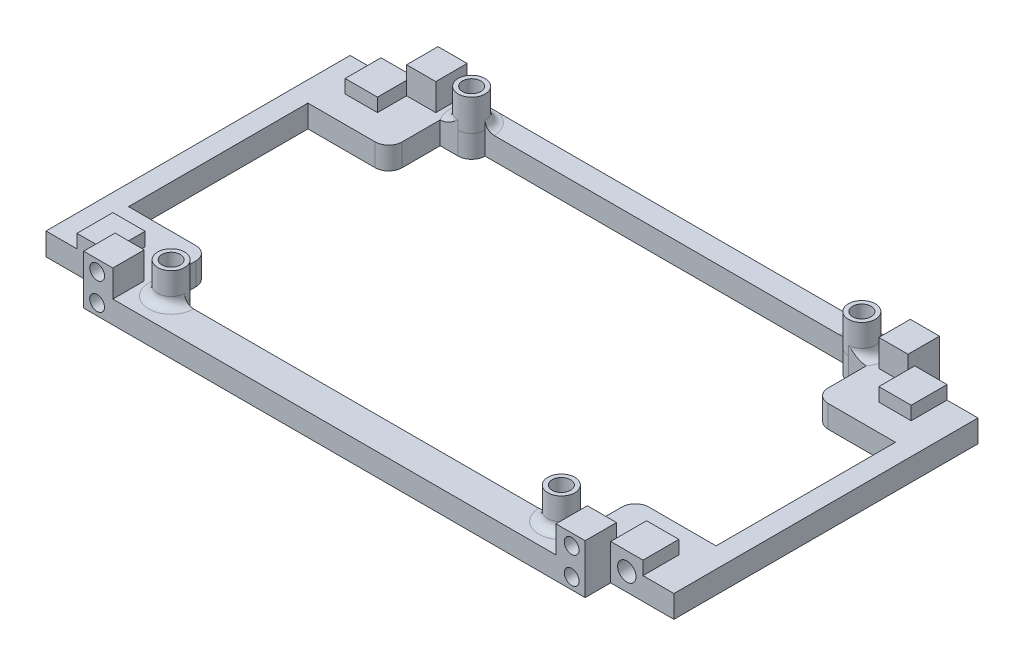
SolidWorks part; units mm, degrees
ref_plane "Front Plane" through (0, 0, 0) normal (0, 0, 1) x (1, 0, 0)
ref_plane "Top Plane" through (0, 0, 0) normal (0, 1, 0) x (1, 0, 0)
ref_plane "Right Plane" through (0, 0, 0) normal (1, 0, 0) x (0, 0, -1)
sketch "Sketch1" plane through (0, 0, 0) normal (0, 1, 0) x (1, 0, 0)
  line L0 (-70, -33.9) -> (-70, 33.9)
  line L1 (-70, -41) -> (70, -41) construction
  line L2 (-70, -41) -> (-70, 41) construction
  line L3 (-70, 41) -> (70, 41) construction
  line L4 (70, -41) -> (70, 41) construction
  line L5 (-70, -41) -> (70, 41) construction
  line L6 (-70, 41) -> (70, -41) construction
  line L7 (-70, 33.9) -> (-55.9, 33.9)
  line L8 (-55.9, 33.9) -> (-55.9, 41)
  line L9 (-55.9, 41) -> (55.9, 41)
  line L10 (55.9, 41) -> (55.9, 33.9)
  line L11 (55.9, 33.9) -> (70, 33.9)
  line L12 (70, 33.9) -> (70, -33.9)
  line L13 (70, -33.9) -> (55.9, -33.9)
  line L14 (55.9, -33.9) -> (55.9, -41)
  line L15 (55.9, -41) -> (-55.9, -41)
  line L16 (-55.9, -41) -> (-55.9, -33.9)
  line L17 (-55.9, -33.9) -> (-70, -33.9)
  point P0 (0, 0)
  dimension "D1" = 140
  dimension "D2" = 82
  dimension "D3" = 7.1
  dimension "D4" = 14.1
extrude "Boss-Extrude1" add sketch "Sketch1" along normal blind 5
sketch "Sketch3" plane through (0, 5, 0) normal (0, 1, 0) x (1, 0, 0)
  line L1 (-43.5, 34.5) -> (43.5, 34.5) construction
  line L2 (-43.5, 34.5) -> (-43.5, -32.5) construction
  line L3 (-43.5, -32.5) -> (43.5, -32.5) construction
  line L4 (43.5, 34.5) -> (43.5, -32.5) construction
  line L5 (-43.5, 34.5) -> (43.5, -32.5) construction
  line L6 (-43.5, -32.5) -> (43.5, 34.5) construction
  circle A0 centre (-43.5, -32.5) radius 3
  circle A1 centre (43.5, -32.5) radius 3
  circle A2 centre (43.5, 34.5) radius 3
  circle A3 centre (-43.5, 34.5) radius 3
  point P0 (0, 1)
  dimension "D4" = 6
  dimension "D1" = 87
  dimension "D2" = 67
  dimension "D3" = 1
sketch "Sketch2" plane through (0, 5, 0) normal (0, 1, 0) x (1, 0, 0)
  line L0 (-43.5, 31.5) -> (-40.5, 31.5)
  line L5 (-40.5, -32.5) -> (40.5, -32.5)
  line L6 (-43.5, -29.5) -> (-43.5, 31.5)
  line L7 (-40.5, 34.5) -> (40.5, 34.5)
  line L8 (43.5, -29.5) -> (43.5, 31.5)
  line L9 (-43.5, -32.5) -> (43.5, 34.5) construction
  line L10 (-43.5, 34.5) -> (43.5, -32.5) construction
  line L11 (-40.5, 31.5) -> (-40.5, 34.5)
  line L12 (40.5, 34.5) -> (40.5, 31.5)
  line L13 (40.5, 31.5) -> (43.5, 31.5)
  line L14 (43.5, -29.5) -> (40.5, -29.5)
  line L15 (40.5, -29.5) -> (40.5, -32.5)
  line L16 (-40.5, -32.5) -> (-40.5, -29.5)
  line L17 (-40.5, -29.5) -> (-43.5, -29.5)
  line L18 (43.5, -32.5) -> (-43.5, -32.5) construction
  line L19 (-43.5, -32.5) -> (-43.5, 34.5) construction
  line L20 (-43.5, 34.5) -> (43.5, 34.5) construction
  line L21 (43.5, 34.5) -> (43.5, -32.5) construction
  point P0 (0, 0)
  point P1 (0, 1)
  dimension "D1" = 3
extrude "Cut-Extrude1" cut sketch "Sketch2" against normal through all
extrude "Boss-Extrude2" add sketch "Sketch3" along normal blind 7
sketch "Sketch4" plane through (0, 12, 0) normal (0, 1, 0) x (1, 0, 0)
  circle A0 centre (-43.5, 34.5) radius 2.05
  circle A1 centre (43.5, 34.5) radius 2.05
  circle A2 centre (43.5, -32.5) radius 2.05
  circle A3 centre (-43.5, -32.5) radius 2.05
  dimension "D1" = 4.1
extrude "Cut-Extrude2" cut sketch "Sketch4" against normal through all and the other way through all
sketch "Sketch5" plane through (0, 5, 0) normal (0, 1, 0) x (1, 0, 0)
  line L0 (-43.5, -29.5) -> (-40.5, -29.5) construction
  line L1 (-43.5, 31.5) -> (-55.5, 31.5)
  line L2 (-43.5, 31.5) -> (-43.5, -29.5)
  line L3 (-43.5, -29.5) -> (-55.5, -29.5)
  line L4 (-55.5, 31.5) -> (-55.5, -29.5)
  line L5 (0, 34.5) -> (0, -32.5) construction
  line L6 (40.5, 34.5) -> (-40.5, 34.5) construction
  line L7 (-40.5, -32.5) -> (40.5, -32.5) construction
  line L8 (55.5, 31.5) -> (55.5, -29.5)
  line L9 (43.5, -29.5) -> (55.5, -29.5)
  line L10 (43.5, 31.5) -> (43.5, -29.5)
  line L11 (43.5, 31.5) -> (55.5, 31.5)
  dimension "D1" = 12
extrude "Cut-Extrude3" cut sketch "Sketch5" against normal through all
fillet "Fillet1" radius 3 4 edges at (40.5, 2.5, 29.5) (-40.5, 2.5, 29.5) (40.5, 2.5, -31.5) (-40.5, 2.5, -31.5)
sketch "Sketch6" plane through (0, 5, 0) normal (0, 1, 0) x (1, 0, 0)
  line L0 (40.5, 34.5) -> (-40.5, 34.5) construction
  line L1 (-25, 34.5) -> (25, 34.5)
  line L2 (-25, 34.5) -> (-25, 32.5)
  line L3 (-25, 32.5) -> (25, 32.5)
  line L4 (25, 34.5) -> (25, 32.5)
  line L5 (0, -32.5) -> (0, -41) construction
  line L6 (-40.5, -32.5) -> (40.5, -32.5) construction
  line L7 (-55.9, -41) -> (55.9, -41) construction
  line L8 (0, 32.5) -> (0, 41) construction
  line L9 (55.9, 41) -> (-55.9, 41) construction
  point P6 (0, 32.5)
  dimension "D1" = 50
sketch "Sketch7" plane through (0, 5, 0) normal (0, 1, 0) x (1, 0, 0)
  line L0 (0, 41) -> (0, -41) construction
  line L1 (55.9, 33.9) -> (63.1, 33.9)
  line L2 (55.9, 33.9) -> (55.9, 25.9)
  line L3 (55.9, 25.9) -> (63.1, 25.9)
  line L4 (63.1, 33.9) -> (63.1, 25.9)
  line L5 (55.9, 41) -> (-55.9, 41) construction
  line L6 (-55.9, -41) -> (55.9, -41) construction
  line L7 (-70, 0) -> (70, 0) construction
  line L8 (-70, 33.9) -> (-70, -33.9) construction
  line L9 (70, -33.9) -> (70, 33.9) construction
  dimension "D1" = 7.2
  dimension "D2" = 8
extrude "Boss-Extrude3" add sketch "Sketch7" along normal blind 3
sketch "Sketch8" plane through (0, 0, -33.9) normal (0, 0, -1) x (-1, 0, 0)
  line L0 (-63.1, 8) -> (-55.9, 0) construction
  circle A0 centre (-59.5, 4) radius 2.05
  dimension "D1" = 4.1
extrude "Cut-Extrude5" cut sketch "Sketch8" against normal blind 6
mirror "Mirror3" about plane through (0, 0, 0) normal (1, 0, 0) of "Cut-Extrude5", "Boss-Extrude3"
mirror "Mirror4" about plane through (0, 0, 0) normal (0, 0, 1) of "Mirror3"
sketch "Sketch10" plane through (0, 5, 0) normal (0, 1, 0) x (1, 0, 0)
  line L0 (55.9, 33.9) -> (55.9, 41) construction
  line L1 (-55.9, 41) -> (55.9, 41)
  line L2 (-55.9, 41) -> (-55.9, 40)
  line L3 (-55.9, 40) -> (55.9, 40)
  line L4 (55.9, 41) -> (55.9, 40)
  line L5 (-55.9, -33.9) -> (-55.9, -41) construction
  line L6 (55.9, -41) -> (-55.9, -41)
  line L7 (55.9, -41) -> (55.9, -40)
  line L8 (55.9, -40) -> (-55.9, -40)
  line L9 (-55.9, -41) -> (-55.9, -40)
  dimension "D1" = 1
  dimension "D2" = 1
extrude "Cut-Extrude7" cut sketch "Sketch10" against normal through all
fillet "Fillet5" radius 2 4 edges at (45.6213, 5, -36.6213) (45.6213, 5, 34.6213) (-45.6213, 5, 34.6213) (-45.6213, 5, -36.6213)
sketch "Sketch11" plane through (0, 5, 0) normal (0, 1, 0) x (1, 0, 0)
  line L1 (55.5, -29.5) -> (47.5, -29.5)
  line L2 (55.5, -29.5) -> (55.5, 31.5)
  line L3 (55.5, 31.5) -> (47.5, 31.5)
  line L4 (47.5, -29.5) -> (47.5, 31.5)
  line L5 (-47.5, -29.5) -> (-55.5, -29.5)
  line L6 (-47.5, -29.5) -> (-47.5, 31.5)
  line L7 (-47.5, 31.5) -> (-55.5, 31.5)
  line L8 (-55.5, -29.5) -> (-55.5, 31.5)
extrude "Boss-Extrude4" add sketch "Sketch11" against normal up to surface (5 mm away) up to face at (0, 0, 0)
sketch "Sketch12" plane through (0, 5, 0) normal (0, 1, 0) x (1, 0, 0)
  line L0 (47.5, 31.5) -> (47.5, -29.5) construction
  line L1 (47.5, 20) -> (65.5, 20)
  line L2 (47.5, 20) -> (47.5, -20)
  line L3 (47.5, -20) -> (65.5, -20)
  line L4 (65.5, 20) -> (65.5, -20)
  line L5 (70, -33.9) -> (70, 33.9) construction
  point P6 (65.5, 0)
  point P9 (70, 0)
  dimension "D1" = 18
  dimension "D2" = 40
extrude "Cut-Extrude8" cut sketch "Sketch12" against normal through all and the other way through all
mirror "Mirror7" about plane through (0, 0, 0) normal (1, 0, 0) of "Cut-Extrude8"
fillet "Fillet6" radius 3 4 edges at (47.5, 2.5, -20) (47.5, 2.5, 20) (-47.5, 2.5, -20) (-47.5, 2.5, 20)
sketch "Sketch13" plane through (0, 5, 0) normal (0, 1, 0) x (1, 0, 0)
  line L0 (55.9, 33.9) -> (55.9, 40) construction
  line L1 (-55.9, 40) -> (55.9, 40)
  line L2 (-55.9, 40) -> (-55.9, 39.4)
  line L3 (-55.9, 39.4) -> (55.9, 39.4)
  line L4 (55.9, 40) -> (55.9, 39.4)
  line L5 (-55.9, -33.9) -> (-55.9, -40) construction
  line L6 (55.9, -40) -> (-55.9, -40)
  line L7 (55.9, -40) -> (55.9, -39.6)
  line L8 (55.9, -39.6) -> (-55.9, -39.6)
  line L9 (-55.9, -40) -> (-55.9, -39.6)
  dimension "D1" = 0.6
  dimension "D2" = 0.4
extrude "Cut-Extrude9" cut sketch "Sketch13" against normal through all both and the other way through all
sketch "Sketch14" plane through (0, 5, 0) normal (0, 1, 0) x (1, 0, 0)
  line L1 (-55.9, -39.6) -> (-49.4, -39.6)
  line L2 (-55.9, -39.6) -> (-55.9, -32.6)
  line L3 (-55.9, -32.6) -> (-49.4, -32.6)
  line L4 (-49.4, -39.6) -> (-49.4, -32.6)
  line L5 (-55.9, 39.4) -> (-49.4, 39.4)
  line L6 (-55.9, 39.4) -> (-55.9, 32.4)
  line L7 (-55.9, 32.4) -> (-49.4, 32.4)
  line L8 (-49.4, 39.4) -> (-49.4, 32.4)
  dimension "D1" = 6.5
  dimension "D2" = 7
extrude "Boss-Extrude5" add sketch "Sketch14" along normal blind 6
sketch "Sketch15" plane through (0, 0, 39.6) normal (0, 0, 1) x (1, 0, 0)
  line L0 (-49.4, 5) -> (-49.4, 0) construction
  line L1 (55.9, 0) -> (-55.9, 0) construction
  line L3 (-55.9, 0) -> (-55.9, 11) construction
  circle A0 centre (-52.9, 2.5) radius 1.65
  circle A1 centre (-52.9, 8.5) radius 1.65
  point P4 (-49.4, 2.5)
  dimension "D1" = 3.3
  dimension "D2" = 3
  dimension "D3" = 6
extrude "Cut-Extrude10" cut sketch "Sketch15" against normal blind 6
sketch "Sketch16" plane through (0, 0, -39.4) normal (0, 0, -1) x (-1, 0, 0)
  circle A0 centre (52.9, 8.5) radius 1.65 construction
  circle A1 centre (52.9, 2.5) radius 1.65 construction
  circle A2 centre (52.9, 8.5) radius 1.65
  circle A3 centre (52.9, 2.5) radius 1.65
extrude "Cut-Extrude11" cut sketch "Sketch16" against normal blind 6
mirror "Mirror8" about plane through (0, 0, 0) normal (1, 0, 0) of "Cut-Extrude10", "Cut-Extrude11", "Boss-Extrude5"
